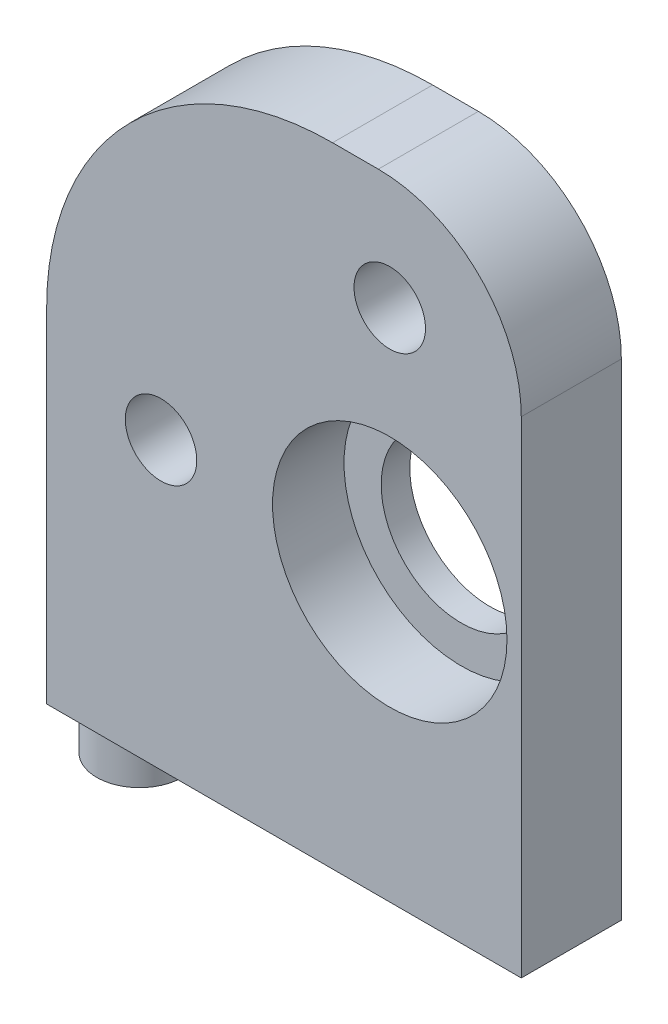
SolidWorks part; units mm, degrees
ref_plane "前视基准面" through (0, 0, 0) normal (0, 0, 1) x (1, 0, 0)
ref_plane "上视基准面" through (0, 0, 0) normal (0, 1, 0) x (1, 0, 0)
ref_plane "右视基准面" through (0, 0, 0) normal (1, 0, 0) x (0, 0, -1)
other "Configuration Table"
sketch "草图1" plane through (0, 0, 0) normal (0, 0, 1) x (1, 0, 0)
  line L1 (-12, 12) -> (4.6, 12)
  line L2 (-12, 12) -> (-12, -10)
  line L3 (-12, -10) -> (4.6, -10)
  line L4 (4.6, 12) -> (4.6, -10)
  circle A0 centre (0, 0) radius 2.8
  circle A1 centre (0, 0) radius 4.1
  circle A2 centre (0, 8) radius 1.25
  circle A3 centre (-8, 0) radius 1.25
  dimension "D1" = 5.6
  dimension "D2" = 8.2
  dimension "D7" = 2.5
  dimension "D9" = 2.5
  dimension "D3" = 12
  dimension "D4" = 12
  dimension "D5" = 10
  dimension "D6" = 4.6
  dimension "D8" = 8
  dimension "D10" = 8
extrude "凸台-拉伸1" add sketch "草图1" along normal blind 3.5 contours L4 L1 L2 L3 A3 A2 A1 region at (-4.3361, 1.0772, 0)
extrude "凸台-拉伸2" add sketch "草图1<3>" along normal blind 1 contours A1 A0 region at (-3.984, 0, 0)
sketch "草图1<3>" plane through (0, 0, 0) normal (0, 0, 1) x (1, 0, 0) same geometry as "草图1"
fillet "圆角1" radius 10 1 edges at (-12, 12, 1.75)
fillet "圆角2" radius 5 1 edges at (4.6, 12, 1.75)
sketch "草图2" plane through (0, -10, 0) normal (0, -1, 0) x (1, 0, 0)
  line L0 (-12, 0) -> (4.6, 0) construction
  line L3 (-12, 3.5) -> (-12, 0) construction
  circle A0 centre (-10.5, 1.75) radius 1.5
  circle A2 centre (-4.5, 1.75) radius 1
  dimension "D1" = 3
  dimension "D3" = 4.5
  dimension "D4" = 2
  dimension "D2" = 1.75
  dimension "D5" = 6
extrude "切除-拉伸1" cut sketch "草图2" against normal blind 6 contours A2 region at (-4.5, -10, 1.75)
extrude "凸台-拉伸3" add sketch "草图2<3>" along normal blind 1.6 contours A0 region at (-10.5, -10, 1.75)
sketch "草图2<3>" plane through (0, -10, 0) normal (0, -1, 0) x (1, 0, 0) same geometry as "草图2"
